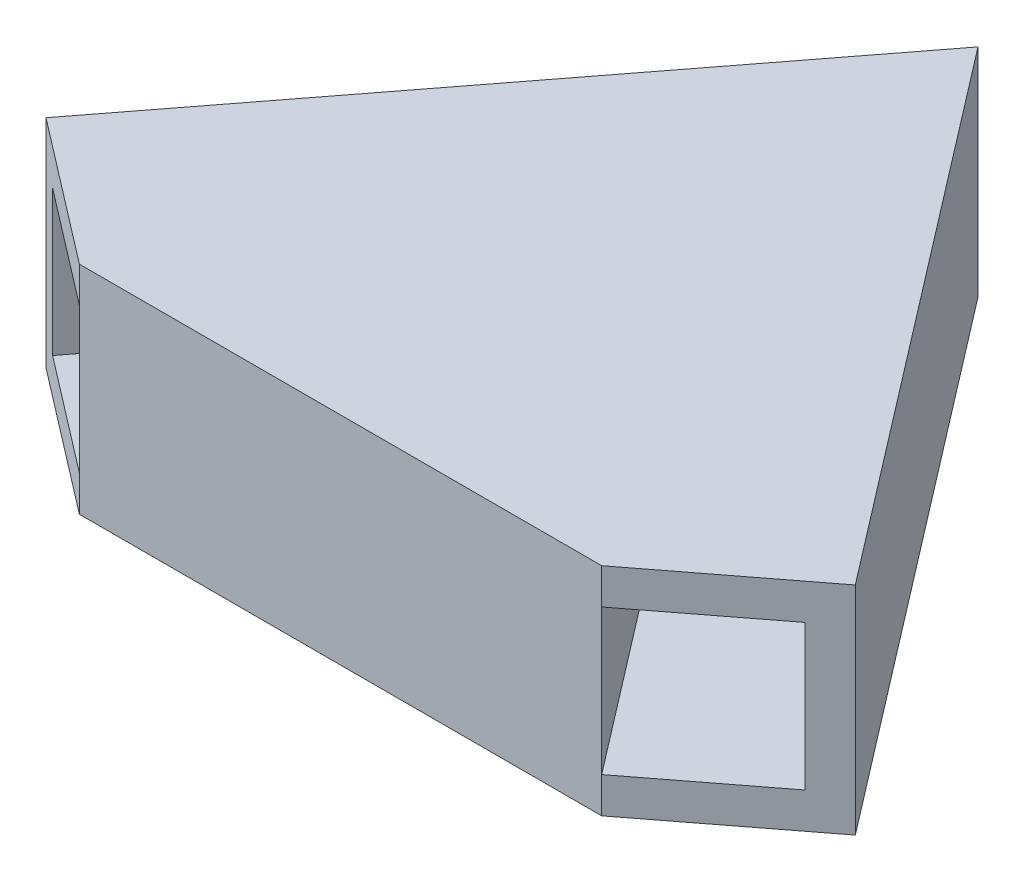
SolidWorks part; units mm, degrees
ref_plane "Front Plane" through (0, 0, 0) normal (0, 0, 1) x (1, 0, 0)
ref_plane "Top Plane" through (0, 0, 0) normal (0, 1, 0) x (1, 0, 0)
ref_plane "Right Plane" through (0, 0, 0) normal (1, 0, 0) x (0, 0, -1)
sketch "Sketch1" plane through (0, 0, 0) normal (0, 1, 0) x (1, 0, 0)
  line L0 (0, 0) -> (-36.5257, -47.6012) construction
  line L1 (0, 0) -> (0, -47.6012) construction
  line L2 (-36.5257, -47.6012) -> (0, -47.6012) construction
  line L3 (-36.5257, -47.6012) -> (-52.6308, -35.2433) construction
  line L4 (0, 0) -> (0, 33.3464) construction
  line L5 (-52.6308, -35.2433) -> (0, 33.3464) construction
  line L6 (-52.6308, -35.2433) -> (-56.5975, -32.1995) construction
  line L7 (0, 33.3464) -> (0, 41.5598) construction
  line L8 (-56.5975, -32.1995) -> (0, 41.5598) construction
  arc A0 (-8.3119, -10.8323) -> (0, -13.6539) centre (0, 0) ccw construction
sketch "Sketch2" plane through (0, 0, 0) normal (0, 1, 0) x (1, 0, 0)
  line L0 (-56.5975, -32.1995) -> (0, 41.5598)
  line L1 (0, 41.5598) -> (0, -47.6012)
  line L2 (0, -47.6012) -> (-36.5257, -47.6012)
  line L3 (-36.5257, -47.6012) -> (-56.5975, -32.1995)
extrude "Boss-Extrude1" add sketch "Sketch2" along normal blind 5
sketch "Sketch4" plane through (0, 5, 0) normal (0, 1, 0) x (1, 0, 0)
  line L0 (-56.5975, -32.1995) -> (-52.6308, -35.2433)
  line L1 (-56.5975, -32.1995) -> (0, 41.5598)
  line L2 (0, 41.5598) -> (0, 33.3464)
  line L3 (0, 33.3464) -> (-52.6308, -35.2433)
extrude "Boss-Extrude2" add sketch "Sketch4" along normal blind 20.3
sketch "Sketch5" plane through (0, 25.3, 0) normal (0, 1, 0) x (1, 0, 0)
  line L0 (-56.5975, -32.1995) -> (-36.5257, -47.6012)
  line L1 (-36.5257, -47.6012) -> (0, -47.6012)
  line L2 (0, -47.6012) -> (0, 41.5598)
  line L3 (0, 41.5598) -> (-56.5975, -32.1995)
extrude "Boss-Extrude3" add sketch "Sketch5" along normal blind 5
sketch "Sketch6" plane through (0, 5, 0) normal (0, 1, 0) x (1, 0, 0)
  line L0 (-36.5257, -47.6012) -> (0, 0) construction
  line L1 (0, -47.6012) -> (0, 33.3464) construction
  line L2 (-52.6308, -35.2433) -> (0, 33.3464) construction
  line L3 (0, 0) -> (-16.1051, 12.3579) construction
  line L4 (0, 0) -> (-2.5, 0) construction
  line L5 (-17.0315, 11.1504) -> (0, -1.9183)
  line L6 (-17.0315, 11.1504) -> (0, 33.3464)
  line L7 (0, -1.9183) -> (0, 33.3464)
extrude "Boss-Extrude4" add sketch "Sketch6" along normal up to surface (20.3 mm away) up to face at (-22.2891, 25.3, 24.2748)
sketch "Sketch7" plane through (0, 5, 0) normal (0, 1, 0) x (1, 0, 0)
  line L0 (-36.5257, -47.6012) -> (-0.9265, -1.2074)
  line L1 (-17.0315, 11.1504) -> (0, -1.9183) construction
  line L2 (0, -1.9183) -> (0, -47.6012)
  line L3 (0, -47.6012) -> (-36.5257, -47.6012)
  line L4 (-0.9265, -1.2074) -> (0, -1.9183)
extrude "Boss-Extrude5" add sketch "Sketch7" along normal up to surface (20.3 mm away) up to face at (-21.2376, 25.3, 24.2427)
mirror "Mirror2" about plane through (0, 5, -41.5598) normal (-1, 0, 0) of "Boss-Extrude5", "Boss-Extrude4", "Boss-Extrude3", "Boss-Extrude2", "Boss-Extrude1"
